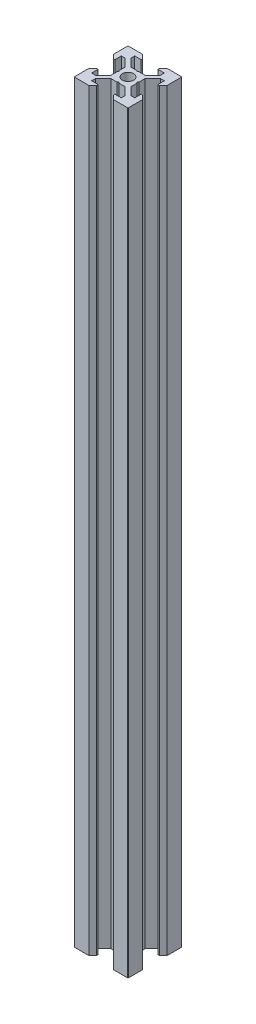
SolidWorks part; units mm, degrees
ref_plane "Plan de face" through (0, 0, 0) normal (0, 0, 1) x (1, 0, 0)
ref_plane "Plan de dessus" through (0, 0, 0) normal (0, 1, 0) x (1, 0, 0)
ref_plane "Plan de droite" through (0, 0, 0) normal (1, 0, 0) x (0, 0, -1)
sketch "Esquisse1" plane through (0, 0, 0) normal (0, 1, 0) x (1, 0, 0)
  line L0 (0, -68.4) -> (0, 76.1968) construction
  line L1 (-68.4, 0) -> (76.1968, 0) construction
  line L2 (0, 0) -> (13.0871, 13.0871) construction
  line L4 (3.7, 2.6393) -> (6.5607, 5.5)
  line L5 (6.5607, 5.5) -> (8, 5.5)
  line L6 (8, 5.5) -> (8, 3.1)
  line L7 (8, 3.1) -> (8.52, 3.1)
  line L8 (8.52, 3.1) -> (10, 4.58)
  line L9 (10, 4.58) -> (10, 9.82)
  line L10 (0.3536, 3.7) -> (0, 3.3464)
  line L60 (3.7, 2.6393) -> (3.7, 0.3536)
  line L61 (3.7, 0.3536) -> (3.3464, 0)
  line L62 (2.6393, 3.7) -> (0.3536, 3.7)
  line L63 (4.58, 10) -> (9.82, 10)
  line L64 (3.1, 8.52) -> (4.58, 10)
  line L65 (3.1, 8) -> (3.1, 8.52)
  line L66 (5.5, 8) -> (3.1, 8)
  line L67 (5.5, 6.5607) -> (5.5, 8)
  line L68 (2.6393, 3.7) -> (5.5, 6.5607)
  line L69 (2.6393, -3.7) -> (5.5, -6.5607)
  line L70 (5.5, -6.5607) -> (5.5, -8)
  line L71 (5.5, -8) -> (3.1, -8)
  line L72 (3.1, -8) -> (3.1, -8.52)
  line L73 (3.1, -8.52) -> (4.58, -10)
  line L74 (4.58, -10) -> (9.82, -10)
  line L75 (3.7, -0.3536) -> (3.3464, 0)
  line L76 (2.6393, -3.7) -> (0.3536, -3.7)
  line L77 (0.3536, -3.7) -> (0, -3.3464)
  line L78 (3.7, -2.6393) -> (3.7, -0.3536)
  line L79 (10, -4.58) -> (10, -9.82)
  line L80 (8.52, -3.1) -> (10, -4.58)
  line L81 (8, -3.1) -> (8.52, -3.1)
  line L82 (8, -5.5) -> (8, -3.1)
  line L83 (6.5607, -5.5) -> (8, -5.5)
  line L84 (3.7, -2.6393) -> (6.5607, -5.5)
  line L85 (-3.7, -2.6393) -> (-6.5607, -5.5)
  line L86 (-6.5607, -5.5) -> (-8, -5.5)
  line L87 (-8, -5.5) -> (-8, -3.1)
  line L88 (-8, -3.1) -> (-8.52, -3.1)
  line L89 (-8.52, -3.1) -> (-10, -4.58)
  line L90 (-10, -4.58) -> (-10, -9.82)
  line L91 (-0.3536, -3.7) -> (0, -3.3464)
  line L92 (-3.7, -2.6393) -> (-3.7, -0.3536)
  line L93 (-3.7, -0.3536) -> (-3.3464, 0)
  line L94 (-2.6393, -3.7) -> (-0.3536, -3.7)
  line L95 (-4.58, -10) -> (-9.82, -10)
  line L96 (-3.1, -8.52) -> (-4.58, -10)
  line L97 (-3.1, -8) -> (-3.1, -8.52)
  line L98 (-5.5, -8) -> (-3.1, -8)
  line L99 (-5.5, -6.5607) -> (-5.5, -8)
  line L100 (-2.6393, -3.7) -> (-5.5, -6.5607)
  line L101 (-2.6393, 3.7) -> (-5.5, 6.5607)
  line L102 (-5.5, 6.5607) -> (-5.5, 8)
  line L103 (-5.5, 8) -> (-3.1, 8)
  line L104 (-3.1, 8) -> (-3.1, 8.52)
  line L105 (-3.1, 8.52) -> (-4.58, 10)
  line L106 (-4.58, 10) -> (-9.82, 10)
  line L107 (-3.7, 0.3536) -> (-3.3464, 0)
  line L108 (-2.6393, 3.7) -> (-0.3536, 3.7)
  line L109 (-0.3536, 3.7) -> (0, 3.3464)
  line L110 (-3.7, 2.6393) -> (-3.7, 0.3536)
  line L111 (-10, 4.58) -> (-10, 9.82)
  line L112 (-8.52, 3.1) -> (-10, 4.58)
  line L113 (-8, 3.1) -> (-8.52, 3.1)
  line L114 (-8, 5.5) -> (-8, 3.1)
  line L115 (-6.5607, 5.5) -> (-8, 5.5)
  line L116 (-3.7, 2.6393) -> (-6.5607, 5.5)
  circle A0 centre (0, 0) radius 2.1
  arc A1 (10, 9.82) -> (9.82, 10) centre (9.82, 9.82) ccw
  arc A2 (9.82, -10) -> (10, -9.82) centre (9.82, -9.82) ccw
  arc A3 (-10, -9.82) -> (-9.82, -10) centre (-9.82, -9.82) ccw
  arc A4 (-9.82, 10) -> (-10, 9.82) centre (-9.82, 9.82) ccw
  point P27 (10, 10)
  point P28 (10, 10)
  point P47 (10, -10)
  point P48 (0, 0)
  point P68 (-10, -10)
  point P69 (0, 0)
  point P74 (0, 0)
  point P92 (-10, 10)
  point P93 (0, 0)
  point P96 (0, 0)
  dimension "D9" = 4.2
  dimension "D11" = 4
  dimension "D10" = 0.18
  dimension "D1" = 45
  dimension "D2" = 4.3
  dimension "D3" = 10
  dimension "D4" = 0.75
  dimension "D5" = 3.1
  dimension "D6" = 5.5
  dimension "D7" = 4.58
  dimension "D8" = 2
  dimension "D12" = 0.5
extrude "Boss.-Extru.1" add sketch "Esquisse1" along normal blind 280
